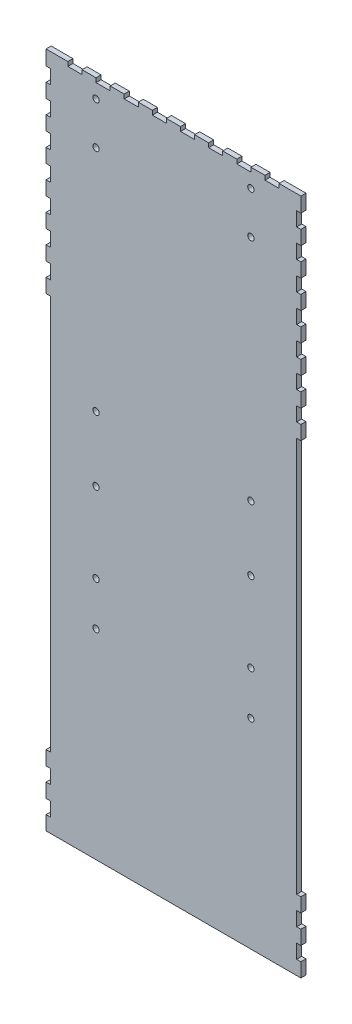
SolidWorks part; units mm, degrees
ref_plane "Front Plane" through (0, 0, 0) normal (0, 0, 1) x (1, 0, 0)
ref_plane "Top Plane" through (0, 0, 0) normal (0, 1, 0) x (1, 0, 0)
ref_plane "Right Plane" through (0, 0, 0) normal (1, 0, 0) x (0, 0, -1)
sketch "Sketch1" plane through (0, 0, 0) normal (0, 0, 1) x (1, 0, 0)
  line L2 (3, 408) -> (-12.5, 408)
  line L3 (-178, 408) -> (-178, 397.5)
  line L4 (-175, 0) -> (0, 0)
  line L5 (0, 0) -> (0, 405)
  line L6 (0, 405) -> (-175, 405)
  line L7 (-175, 405) -> (-175, 0)
  line L8 (-175, 0) -> (0, 0) construction
  line L10 (0, 405) -> (-175, 405) construction
  line L11 (-175, 405) -> (-175, 0) construction
  line L12 (-178, 397.5) -> (-175, 397.5)
  line L13 (-175, 397.5) -> (-175, 387.5)
  line L14 (-175, 387.5) -> (-178, 387.5)
  line L15 (-178, 387.5) -> (-178, 377.5)
  line L16 (-178, 408) -> (-178, -3) construction
  line L17 (-87.5, 408) -> (-87.5, -3) construction
  line L18 (-178, 377.5) -> (-175, 377.5)
  line L19 (-175, 377.5) -> (-175, 367.5)
  line L20 (-175, 367.5) -> (-178, 367.5)
  line L21 (-178, 357.5) -> (-175, 357.5)
  line L22 (-175, 357.5) -> (-175, 347.5)
  line L23 (-175, 347.5) -> (-178, 347.5)
  line L24 (-178, 337.5) -> (-175, 337.5)
  line L25 (-175, 337.5) -> (-175, 327.5)
  line L26 (-175, 327.5) -> (-178, 327.5)
  line L27 (-178, 317.5) -> (-175, 317.5)
  line L28 (-175, 317.5) -> (-175, 307.5)
  line L29 (-175, 307.5) -> (-178, 307.5)
  line L30 (-178, 297.5) -> (-175, 297.5)
  line L31 (-175, 297.5) -> (-175, 287.5)
  line L32 (-175, 287.5) -> (-178, 287.5)
  line L33 (-178, 277.5) -> (-175, 277.5)
  line L34 (-175, 277.5) -> (-175, 267.5)
  line L35 (-175, 267.5) -> (-178, 267.5)
  line L75 (-178, 367.5) -> (-178, 357.5)
  line L76 (-178, 347.5) -> (-178, 337.5)
  line L77 (-178, 327.5) -> (-178, 317.5)
  line L78 (-178, 307.5) -> (-178, 297.5)
  line L79 (-178, 287.5) -> (-178, 277.5)
  line L94 (3, -3) -> (3, 408) construction
  line L95 (0, 0) -> (0, 405) construction
  line L96 (0, 405) -> (0, 0) construction
  line L111 (3, 287.5) -> (3, 277.5)
  line L112 (3, 307.5) -> (3, 297.5)
  line L113 (3, 327.5) -> (3, 317.5)
  line L114 (3, 347.5) -> (3, 337.5)
  line L115 (3, 367.5) -> (3, 357.5)
  line L155 (0, 267.5) -> (3, 267.5)
  line L156 (0, 277.5) -> (0, 267.5)
  line L157 (3, 277.5) -> (0, 277.5)
  line L158 (0, 287.5) -> (3, 287.5)
  line L159 (0, 297.5) -> (0, 287.5)
  line L160 (3, 297.5) -> (0, 297.5)
  line L161 (0, 307.5) -> (3, 307.5)
  line L162 (0, 317.5) -> (0, 307.5)
  line L163 (3, 317.5) -> (0, 317.5)
  line L164 (0, 327.5) -> (3, 327.5)
  line L165 (0, 337.5) -> (0, 327.5)
  line L166 (3, 337.5) -> (0, 337.5)
  line L167 (0, 347.5) -> (3, 347.5)
  line L168 (0, 357.5) -> (0, 347.5)
  line L169 (3, 357.5) -> (0, 357.5)
  line L170 (0, 367.5) -> (3, 367.5)
  line L171 (0, 377.5) -> (0, 367.5)
  line L172 (3, 377.5) -> (0, 377.5)
  line L173 (3, 387.5) -> (3, 377.5)
  line L174 (0, 387.5) -> (3, 387.5)
  line L175 (0, 397.5) -> (0, 387.5)
  line L176 (3, 397.5) -> (0, 397.5)
  line L177 (3, 408) -> (3, 397.5)
  line L178 (-162.5, 408) -> (-162.5, 405)
  line L179 (-162.5, 405) -> (-152.5, 405)
  line L180 (-152.5, 405) -> (-152.5, 408)
  line L181 (-162.5, 408) -> (-178, 408)
  line L182 (3, 408) -> (-178, 408) construction
  line L183 (-142.5, 408) -> (-142.5, 405)
  line L184 (-132.5, 405) -> (-132.5, 408)
  line L185 (-142.5, 405) -> (-132.5, 405)
  line L186 (-122.5, 408) -> (-122.5, 405)
  line L187 (-112.5, 405) -> (-112.5, 408)
  line L188 (-122.5, 405) -> (-112.5, 405)
  line L189 (-102.5, 408) -> (-102.5, 405)
  line L190 (-92.5, 405) -> (-92.5, 408)
  line L191 (-102.5, 405) -> (-92.5, 405)
  line L192 (-82.5, 408) -> (-82.5, 405)
  line L193 (-72.5, 405) -> (-72.5, 408)
  line L194 (-82.5, 405) -> (-72.5, 405)
  line L195 (-62.5, 408) -> (-62.5, 405)
  line L196 (-52.5, 405) -> (-52.5, 408)
  line L197 (-62.5, 405) -> (-52.5, 405)
  line L198 (-42.5, 408) -> (-42.5, 405)
  line L199 (-32.5, 405) -> (-32.5, 408)
  line L200 (-42.5, 405) -> (-32.5, 405)
  line L201 (-22.5, 408) -> (-22.5, 405)
  line L202 (-12.5, 405) -> (-12.5, 408)
  line L203 (-22.5, 405) -> (-12.5, 405)
  line L204 (-142.5, 408) -> (-152.5, 408)
  line L205 (-122.5, 408) -> (-132.5, 408)
  line L206 (-102.5, 408) -> (-112.5, 408)
  line L207 (-82.5, 408) -> (-92.5, 408)
  line L208 (-62.5, 408) -> (-72.5, 408)
  line L209 (-42.5, 408) -> (-52.5, 408)
  line L210 (-22.5, 408) -> (-32.5, 408)
  line L211 (-178, 262.5) -> (-192.1885, 262.5) construction
  line L213 (-175, 247.5) -> (-178, 247.5) [skipped]
  line L214 (-178, 237.5) -> (-175, 237.5) [skipped]
  line L215 (-175, 237.5) -> (-175, 227.5) [skipped]
  line L216 (-175, 227.5) -> (-178, 227.5) [skipped]
  line L217 (-178, 217.5) -> (-175, 217.5) [skipped]
  line L218 (-175, 217.5) -> (-175, 207.5) [skipped]
  line L219 (-175, 207.5) -> (-178, 207.5) [skipped]
  line L220 (-178, 197.5) -> (-175, 197.5) [skipped]
  line L221 (-175, 197.5) -> (-175, 187.5) [skipped]
  line L222 (-175, 187.5) -> (-178, 187.5) [skipped]
  line L223 (-178, 177.5) -> (-175, 177.5) [skipped]
  line L224 (-175, 177.5) -> (-175, 167.5) [skipped]
  line L225 (-175, 167.5) -> (-178, 167.5) [skipped]
  line L226 (-178, 157.5) -> (-175, 157.5) [skipped]
  line L227 (-175, 157.5) -> (-175, 147.5) [skipped]
  line L228 (-175, 147.5) -> (-178, 147.5) [skipped]
  line L229 (-178, 137.5) -> (-175, 137.5) [skipped]
  line L230 (-175, 137.5) -> (-175, 127.5) [skipped]
  line L231 (-175, 127.5) -> (-178, 127.5) [skipped]
  line L232 (-178, 117.5) -> (-175, 117.5) [skipped]
  line L233 (-175, 117.5) -> (-175, 107.5) [skipped]
  line L234 (-175, 107.5) -> (-178, 107.5) [skipped]
  line L235 (-178, 97.5) -> (-175, 97.5) [skipped]
  line L236 (-175, 97.5) -> (-175, 87.5) [skipped]
  line L237 (-175, 87.5) -> (-178, 87.5) [skipped]
  line L238 (-178, 77.5) -> (-175, 77.5) [skipped]
  line L239 (-175, 77.5) -> (-175, 67.5) [skipped]
  line L240 (-175, 67.5) -> (-178, 67.5) [skipped]
  line L241 (-178, 57.5) -> (-175, 57.5) [skipped]
  line L242 (-175, 57.5) -> (-175, 47.5) [skipped]
  line L243 (-175, 47.5) -> (-178, 47.5) [skipped]
  line L244 (-178, 37.5) -> (-175, 37.5) [skipped]
  line L245 (-175, 37.5) -> (-175, 27.5) [skipped]
  line L246 (-175, 27.5) -> (-178, 27.5) [skipped]
  line L247 (-178, 17.5) -> (-175, 17.5) [skipped]
  line L248 (-175, 17.5) -> (-175, 7.5) [skipped]
  line L249 (-175, 7.5) -> (-178, 7.5) [skipped]
  line L250 (-175, 257.5) -> (-175, 247.5) [skipped]
  line L251 (-178, 257.5) -> (-175, 257.5) [skipped]
  line L254 (-178, -73) -> (3, -73)
  line L256 (-178, -3) -> (3, -3) construction
  line L257 (-178, -3) -> (3, -3) construction
  line L258 (-178, 267.5) -> (-178, 257.5)
  line L259 (-178, 257.5) -> (-175, 257.5)
  line L260 (3, 267.5) -> (3, 257.5)
  line L261 (3, 257.5) -> (0, 257.5)
  line L262 (-175, 257.5) -> (-175, 0)
  line L267 (0, 0) -> (0, 257.5)
  line L269 (-178, -23) -> (-175, -23)
  line L270 (-175, -23) -> (-175, 0)
  line L272 (3, -23) -> (0, -23)
  line L273 (0, -23) -> (0, 0)
  line L274 (-178, -33) -> (-175, -33)
  line L275 (-175, -33) -> (-175, -43)
  line L276 (-175, -43) -> (-178, -43)
  line L277 (-178, -43) -> (-178, -53)
  line L278 (-178, -53) -> (-175, -53)
  line L279 (-175, -53) -> (-175, -63)
  line L280 (-175, -63) -> (-178, -63)
  line L281 (-178, -33) -> (-178, -23)
  line L282 (-178, -73) -> (-178, -63)
  line L283 (3, -33) -> (0, -33)
  line L284 (0, -33) -> (0, -43)
  line L285 (0, -43) -> (3, -43)
  line L286 (3, -43) -> (3, -53)
  line L287 (3, -53) -> (0, -53)
  line L288 (0, -53) -> (0, -63)
  line L289 (0, -63) -> (3, -63)
  line L290 (3, -33) -> (3, -23)
  line L291 (3, -73) -> (3, -63)
  dimension "D3" = 10.5
  dimension "D4" = 10
  dimension "D6" = 10
  dimension "D7" = 10
  dimension "D8" = 15.5
  dimension "D10" = 10
  dimension "D11" = 481
  dimension "D12" = 10
  dimension "D13" = 50
  dimension "D14" = 50
  dimension "D15" = 3
  dimension "D16" = 3
  dimension "D17" = 3
  dimension "D18" = 10
  dimension "D19" = 10
  dimension "D20" = 10
  dimension "D21" = 10
  dimension "D22" = 10
  dimension "D23" = 10
  dimension "D24" = 10
  dimension "D25" = 10
  dimension "D26" = 10
  dimension "D27" = 10
  dimension "D28" = 10
  dimension "D1" = 0
  dimension "D2" = 3
  dimension "D5" = 20
  dimension "D9" = 8
extrude "Boss-Extrude1" add sketch "Sketch1" along normal blind 3.6
sketch "Sketch2" plane through (0, 0, 3.6) normal (0, 0, 1) x (1, 0, 0)
  line L116 (-175, 257.5) -> (-175, -23)
  line L117 (-175, -23) -> (-178, -23)
  line L118 (-178, -23) -> (-178, -33)
  line L119 (-178, -33) -> (-175, -33)
  line L120 (-175, -33) -> (-175, -43)
  line L121 (-175, -43) -> (-178, -43)
  line L122 (-178, -43) -> (-178, -53)
  line L123 (-178, -53) -> (-175, -53)
  line L124 (-175, -53) -> (-175, -63)
  line L125 (-175, -63) -> (-178, -63)
  line L126 (-178, -63) -> (-178, -73)
  line L127 (-178, -73) -> (3, -73)
  line L128 (3, -73) -> (3, -63)
  line L129 (3, -63) -> (0, -63)
  line L130 (0, -63) -> (0, -53)
  line L131 (0, -53) -> (3, -53)
  line L132 (3, -53) -> (3, -43)
  line L133 (3, -43) -> (0, -43)
  line L134 (0, -43) -> (0, -33)
  line L135 (0, -33) -> (3, -33)
  line L136 (3, -33) -> (3, -23)
  line L137 (3, -23) -> (0, -23)
  line L138 (0, -23) -> (0, 257.5)
  line L139 (0, 257.5) -> (3, 257.5)
  line L140 (3, 257.5) -> (3, 267.5)
  line L141 (3, 267.5) -> (0, 267.5)
  line L142 (0, 267.5) -> (0, 277.5)
  line L143 (0, 277.5) -> (3, 277.5)
  line L144 (3, 277.5) -> (3, 287.5)
  line L145 (3, 287.5) -> (0, 287.5)
  line L146 (0, 287.5) -> (0, 297.5)
  line L147 (0, 297.5) -> (3, 297.5)
  line L148 (3, 297.5) -> (3, 307.5)
  line L149 (3, 307.5) -> (0, 307.5)
  line L150 (0, 307.5) -> (0, 317.5)
  line L151 (0, 317.5) -> (3, 317.5)
  line L152 (3, 317.5) -> (3, 327.5)
  line L153 (3, 327.5) -> (0, 327.5)
  line L154 (0, 327.5) -> (0, 337.5)
  line L155 (0, 337.5) -> (3, 337.5)
  line L156 (3, 337.5) -> (3, 347.5)
  line L157 (3, 347.5) -> (0, 347.5)
  line L158 (0, 347.5) -> (0, 357.5)
  line L159 (0, 357.5) -> (3, 357.5)
  line L160 (3, 357.5) -> (3, 367.5)
  line L161 (3, 367.5) -> (0, 367.5)
  line L162 (0, 367.5) -> (0, 377.5)
  line L163 (0, 377.5) -> (3, 377.5)
  line L164 (3, 377.5) -> (3, 387.5)
  line L165 (3, 387.5) -> (0, 387.5)
  line L166 (0, 387.5) -> (0, 397.5)
  line L167 (0, 397.5) -> (3, 397.5)
  line L168 (3, 397.5) -> (3, 408)
  line L169 (3, 408) -> (-12.5, 408)
  line L170 (-12.5, 408) -> (-12.5, 405)
  line L171 (-12.5, 405) -> (-22.5, 405)
  line L172 (-22.5, 405) -> (-22.5, 408)
  line L173 (-22.5, 408) -> (-32.5, 408)
  line L174 (-32.5, 408) -> (-32.5, 405)
  line L175 (-32.5, 405) -> (-42.5, 405)
  line L176 (-42.5, 405) -> (-42.5, 408)
  line L177 (-42.5, 408) -> (-52.5, 408)
  line L178 (-52.5, 408) -> (-52.5, 405)
  line L179 (-52.5, 405) -> (-62.5, 405)
  line L180 (-62.5, 405) -> (-62.5, 408)
  line L181 (-62.5, 408) -> (-72.5, 408)
  line L182 (-72.5, 408) -> (-72.5, 405)
  line L183 (-72.5, 405) -> (-82.5, 405)
  line L184 (-82.5, 405) -> (-82.5, 408)
  line L185 (-82.5, 408) -> (-92.5, 408)
  line L186 (-92.5, 408) -> (-92.5, 405)
  line L187 (-92.5, 405) -> (-102.5, 405)
  line L188 (-102.5, 405) -> (-102.5, 408)
  line L189 (-102.5, 408) -> (-112.5, 408)
  line L190 (-112.5, 408) -> (-112.5, 405)
  line L191 (-112.5, 405) -> (-122.5, 405)
  line L192 (-122.5, 405) -> (-122.5, 408)
  line L193 (-122.5, 408) -> (-132.5, 408)
  line L194 (-132.5, 408) -> (-132.5, 405)
  line L195 (-132.5, 405) -> (-142.5, 405)
  line L196 (-142.5, 405) -> (-142.5, 408)
  line L197 (-142.5, 408) -> (-152.5, 408)
  line L198 (-152.5, 408) -> (-152.5, 405)
  line L199 (-152.5, 405) -> (-162.5, 405)
  line L200 (-162.5, 405) -> (-162.5, 408)
  line L201 (-162.5, 408) -> (-178, 408)
  line L202 (-178, 408) -> (-178, 397.5)
  line L203 (-178, 397.5) -> (-175, 397.5)
  line L204 (-175, 397.5) -> (-175, 387.5)
  line L205 (-175, 387.5) -> (-178, 387.5)
  line L206 (-178, 387.5) -> (-178, 377.5)
  line L207 (-178, 377.5) -> (-175, 377.5)
  line L208 (-175, 377.5) -> (-175, 367.5)
  line L209 (-175, 367.5) -> (-178, 367.5)
  line L210 (-178, 367.5) -> (-178, 357.5)
  line L211 (-178, 357.5) -> (-175, 357.5)
  line L212 (-175, 357.5) -> (-175, 347.5)
  line L213 (-175, 347.5) -> (-178, 347.5)
  line L214 (-178, 347.5) -> (-178, 337.5)
  line L215 (-178, 337.5) -> (-175, 337.5)
  line L216 (-175, 337.5) -> (-175, 327.5)
  line L217 (-175, 327.5) -> (-178, 327.5)
  line L218 (-178, 327.5) -> (-178, 317.5)
  line L219 (-178, 317.5) -> (-175, 317.5)
  line L220 (-175, 317.5) -> (-175, 307.5)
  line L221 (-175, 307.5) -> (-178, 307.5)
  line L222 (-178, 307.5) -> (-178, 297.5)
  line L223 (-178, 297.5) -> (-175, 297.5)
  line L224 (-175, 297.5) -> (-175, 287.5)
  line L225 (-175, 287.5) -> (-178, 287.5)
  line L226 (-178, 287.5) -> (-178, 277.5)
  line L227 (-178, 277.5) -> (-175, 277.5)
  line L228 (-175, 277.5) -> (-175, 267.5)
  line L229 (-175, 267.5) -> (-178, 267.5)
  line L230 (-178, 267.5) -> (-178, 257.5)
  line L231 (-178, 257.5) -> (-175, 257.5)
  line L232 (-175, 257.5) -> (-175, -23)
  line L233 (-175, -23) -> (-178, -23)
  line L234 (-178, -23) -> (-178, -33)
  line L235 (-178, -33) -> (-175, -33)
  line L236 (-175, -33) -> (-175, -43)
  line L237 (-175, -43) -> (-178, -43)
  line L238 (-178, -43) -> (-178, -53)
  line L239 (-178, -53) -> (-175, -53)
  line L240 (-175, -53) -> (-175, -63)
  line L241 (-175, -63) -> (-178, -63)
  line L242 (-178, -63) -> (-178, -73)
  line L243 (-178, -73) -> (3, -73)
  line L244 (3, -73) -> (3, -63)
  line L245 (3, -63) -> (0, -63)
  line L246 (0, -63) -> (0, -53)
  line L247 (0, -53) -> (3, -53)
  line L248 (3, -53) -> (3, -43)
  line L249 (3, -43) -> (0, -43)
  line L250 (0, -43) -> (0, -33)
  line L251 (0, -33) -> (3, -33)
  line L252 (3, -33) -> (3, -23)
  line L253 (3, -23) -> (0, -23)
  line L254 (0, -23) -> (0, 257.5)
  line L255 (0, 257.5) -> (3, 257.5)
  line L256 (3, 257.5) -> (3, 267.5)
  line L257 (3, 267.5) -> (0, 267.5)
  line L258 (0, 267.5) -> (0, 277.5)
  line L259 (0, 277.5) -> (3, 277.5)
  line L260 (3, 277.5) -> (3, 287.5)
  line L261 (3, 287.5) -> (0, 287.5)
  line L262 (0, 287.5) -> (0, 297.5)
  line L263 (0, 297.5) -> (3, 297.5)
  line L264 (3, 297.5) -> (3, 307.5)
  line L265 (3, 307.5) -> (0, 307.5)
  line L266 (0, 307.5) -> (0, 317.5)
  line L267 (0, 317.5) -> (3, 317.5)
  line L268 (3, 317.5) -> (3, 327.5)
  line L269 (3, 327.5) -> (0, 327.5)
  line L270 (0, 327.5) -> (0, 337.5)
  line L271 (0, 337.5) -> (3, 337.5)
  line L272 (3, 337.5) -> (3, 347.5)
  line L273 (3, 347.5) -> (0, 347.5)
  line L274 (0, 347.5) -> (0, 357.5)
  line L275 (0, 357.5) -> (3, 357.5)
  line L276 (3, 357.5) -> (3, 367.5)
  line L277 (3, 367.5) -> (0, 367.5)
  line L278 (0, 367.5) -> (0, 377.5)
  line L279 (0, 377.5) -> (3, 377.5)
  line L280 (3, 377.5) -> (3, 387.5)
  line L281 (3, 387.5) -> (0, 387.5)
  line L282 (0, 387.5) -> (0, 397.5)
  line L283 (0, 397.5) -> (3, 397.5)
  line L284 (3, 397.5) -> (3, 408)
  line L285 (3, 408) -> (-12.5, 408)
  line L286 (-12.5, 408) -> (-12.5, 405)
  line L287 (-12.5, 405) -> (-22.5, 405)
  line L288 (-22.5, 405) -> (-22.5, 408)
  line L289 (-22.5, 408) -> (-32.5, 408)
  line L290 (-32.5, 408) -> (-32.5, 405)
  line L291 (-32.5, 405) -> (-42.5, 405)
  line L292 (-42.5, 405) -> (-42.5, 408)
  line L293 (-42.5, 408) -> (-52.5, 408)
  line L294 (-52.5, 408) -> (-52.5, 405)
  line L295 (-52.5, 405) -> (-62.5, 405)
  line L296 (-62.5, 405) -> (-62.5, 408)
  line L297 (-62.5, 408) -> (-72.5, 408)
  line L298 (-72.5, 408) -> (-72.5, 405)
  line L299 (-72.5, 405) -> (-82.5, 405)
  line L300 (-82.5, 405) -> (-82.5, 408)
  line L301 (-82.5, 408) -> (-92.5, 408)
  line L302 (-92.5, 408) -> (-92.5, 405)
  line L303 (-92.5, 405) -> (-102.5, 405)
  line L304 (-102.5, 405) -> (-102.5, 408)
  line L305 (-102.5, 408) -> (-112.5, 408)
  line L306 (-112.5, 408) -> (-112.5, 405)
  line L307 (-112.5, 405) -> (-122.5, 405)
  line L308 (-122.5, 405) -> (-122.5, 408)
  line L309 (-122.5, 408) -> (-132.5, 408)
  line L310 (-132.5, 408) -> (-132.5, 405)
  line L311 (-132.5, 405) -> (-142.5, 405)
  line L312 (-142.5, 405) -> (-142.5, 408)
  line L313 (-142.5, 408) -> (-152.5, 408)
  line L314 (-152.5, 408) -> (-152.5, 405)
  line L315 (-152.5, 405) -> (-162.5, 405)
  line L316 (-162.5, 405) -> (-162.5, 408)
  line L317 (-162.5, 408) -> (-178, 408)
  line L318 (-178, 408) -> (-178, 397.5)
  line L319 (-178, 397.5) -> (-175, 397.5)
  line L320 (-175, 397.5) -> (-175, 387.5)
  line L321 (-175, 387.5) -> (-178, 387.5)
  line L322 (-178, 387.5) -> (-178, 377.5)
  line L323 (-178, 377.5) -> (-175, 377.5)
  line L324 (-175, 377.5) -> (-175, 367.5)
  line L325 (-175, 367.5) -> (-178, 367.5)
  line L326 (-178, 367.5) -> (-178, 357.5)
  line L327 (-178, 357.5) -> (-175, 357.5)
  line L328 (-175, 357.5) -> (-175, 347.5)
  line L329 (-175, 347.5) -> (-178, 347.5)
  line L330 (-178, 347.5) -> (-178, 337.5)
  line L331 (-178, 337.5) -> (-175, 337.5)
  line L332 (-175, 337.5) -> (-175, 327.5)
  line L333 (-175, 327.5) -> (-178, 327.5)
  line L334 (-178, 327.5) -> (-178, 317.5)
  line L335 (-178, 317.5) -> (-175, 317.5)
  line L336 (-175, 317.5) -> (-175, 307.5)
  line L337 (-175, 307.5) -> (-178, 307.5)
  line L338 (-178, 307.5) -> (-178, 297.5)
  line L339 (-178, 297.5) -> (-175, 297.5)
  line L340 (-175, 297.5) -> (-175, 287.5)
  line L341 (-175, 287.5) -> (-178, 287.5)
  line L342 (-178, 287.5) -> (-178, 277.5)
  line L343 (-178, 277.5) -> (-175, 277.5)
  line L344 (-175, 277.5) -> (-175, 267.5)
  line L345 (-175, 267.5) -> (-178, 267.5)
  line L346 (-178, 267.5) -> (-178, 257.5)
  line L347 (-178, 257.5) -> (-175, 257.5)
  dimension "D1" = 0
sketch "Sketch3" plane through (0, 0, 3.6) normal (0, 0, 1) x (1, 0, 0)
  circle A0 centre (-142.5, 365) radius 2.25 construction
  circle A1 centre (-142.5, 365) radius 2.25
  circle A2 centre (-32.5, 69.0494) radius 2.25 construction
  circle A3 centre (-32.5, 100.0494) radius 2.25 construction
  circle A4 centre (-142.5, 69.0494) radius 2.25 construction
  circle A5 centre (-142.5, 100.0494) radius 2.25 construction
  circle A6 centre (-142.5, 156.7198) radius 2.25 construction
  circle A7 centre (-32.5, 156.7198) radius 2.25 construction
  circle A8 centre (-32.5, 202.7198) radius 2.25 construction
  circle A9 centre (-142.5, 202.7198) radius 2.25 construction
  circle A10 centre (-32.5, 365) radius 2.25 construction
  circle A11 centre (-32.5, 395) radius 2.25 construction
  circle A12 centre (-142.5, 395) radius 2.25 construction
  circle A13 centre (-32.5, 69.0494) radius 2.25
  circle A14 centre (-32.5, 100.0494) radius 2.25
  circle A15 centre (-142.5, 69.0494) radius 2.25
  circle A16 centre (-142.5, 100.0494) radius 2.25
  circle A17 centre (-142.5, 156.7198) radius 2.25
  circle A18 centre (-32.5, 156.7198) radius 2.25
  circle A19 centre (-32.5, 202.7198) radius 2.25
  circle A20 centre (-142.5, 202.7198) radius 2.25
  circle A21 centre (-32.5, 365) radius 2.25
  circle A22 centre (-32.5, 395) radius 2.25
  circle A23 centre (-142.5, 395) radius 2.25
extrude "Cut-Extrude1" cut sketch "Sketch3" against normal blind 10
